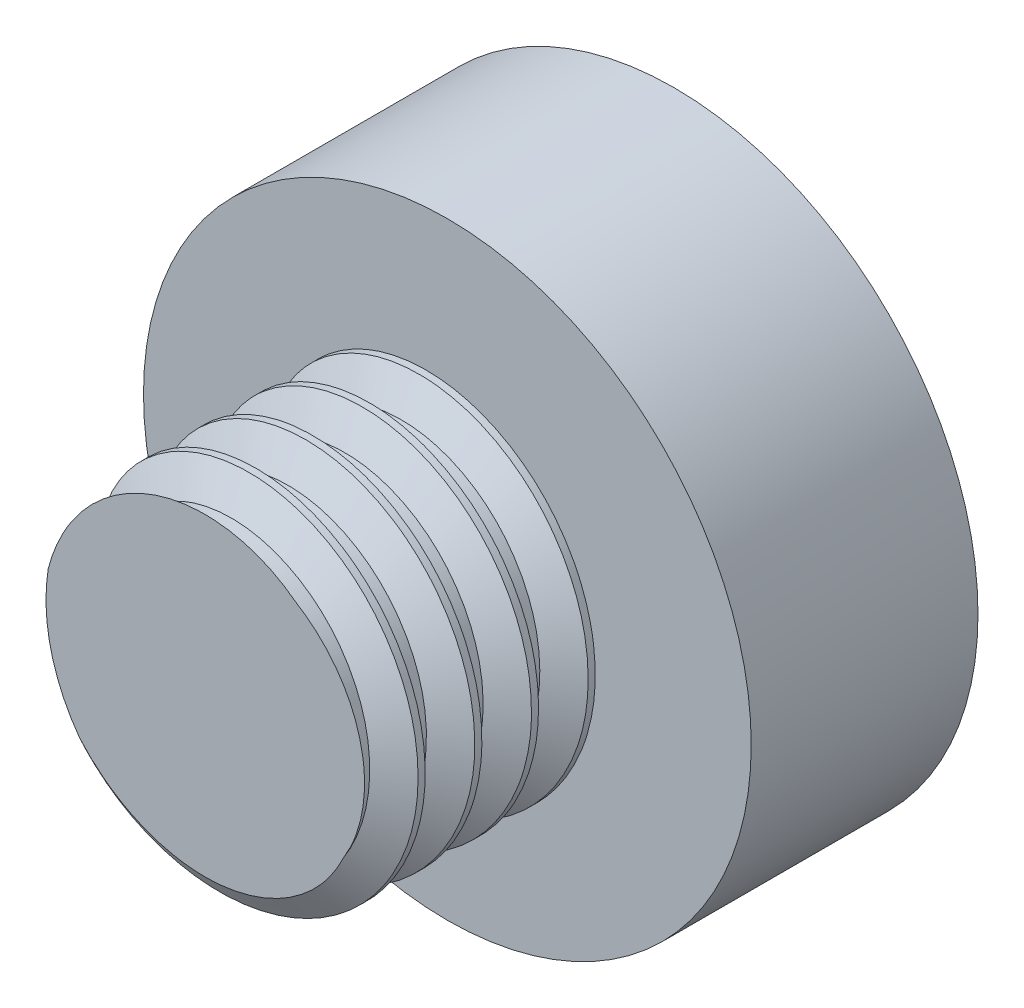
SolidWorks part; units mm, degrees
ref_plane "Front Plane" through (0, 0, 0) normal (0, 0, 1) x (1, 0, 0)
ref_plane "Top Plane" through (0, 0, 0) normal (0, 1, 0) x (1, 0, 0)
ref_plane "Right Plane" through (0, 0, 0) normal (1, 0, 0) x (0, 0, -1)
sketch "Sketch1" plane through (0, 0, 0) normal (0, 0, 1) x (1, 0, 0)
  circle A0 centre (0, 0) radius 17.018
extrude "Boss-Extrude1" add sketch "Sketch1" along normal blind 12.7
sketch "Sketch2" plane through (0, 0, 12.7) normal (0, 0, 1) x (1, 0, 0)
  circle A0 centre (0, 0) radius 9.779
extrude "Boss-Extrude2" add sketch "Sketch2" along normal blind 12.7
thread "Thread1" start angle 0, offset 7.6201, length 0, pitch 3.175, diameter 19.558
ref_plane "Plane1" through (9.779, 0, 5.0799) normal (0, -1, 0) x (1, 0, 0)
sketch "Thread Profile1" plane through (9.779, 0, 5.0799) normal (0, -1, 0) x (1, 0, 0)
  line L0 (0, 0) -> (0, 3.175) construction
  line L11 (0, 0) -> (0, 2.7781)
  line L12 (0, 2.7781) -> (-1.7185, 1.7859)
  line L13 (-1.7185, 1.7859) -> (-1.7185, 0.9922)
  line L15 (-1.7185, 0.9922) -> (0, 0)
  line L17 (-1.7185, 1.3891) -> (0, 1.3891) construction
  point P2 (0, 0)
  dimension "Pitch" = 3.175
  dimension "Profile_Angle" = 60
  dimension "Profile_Land" = 0.7937
  dimension "Profile_Height" = 1.7185
